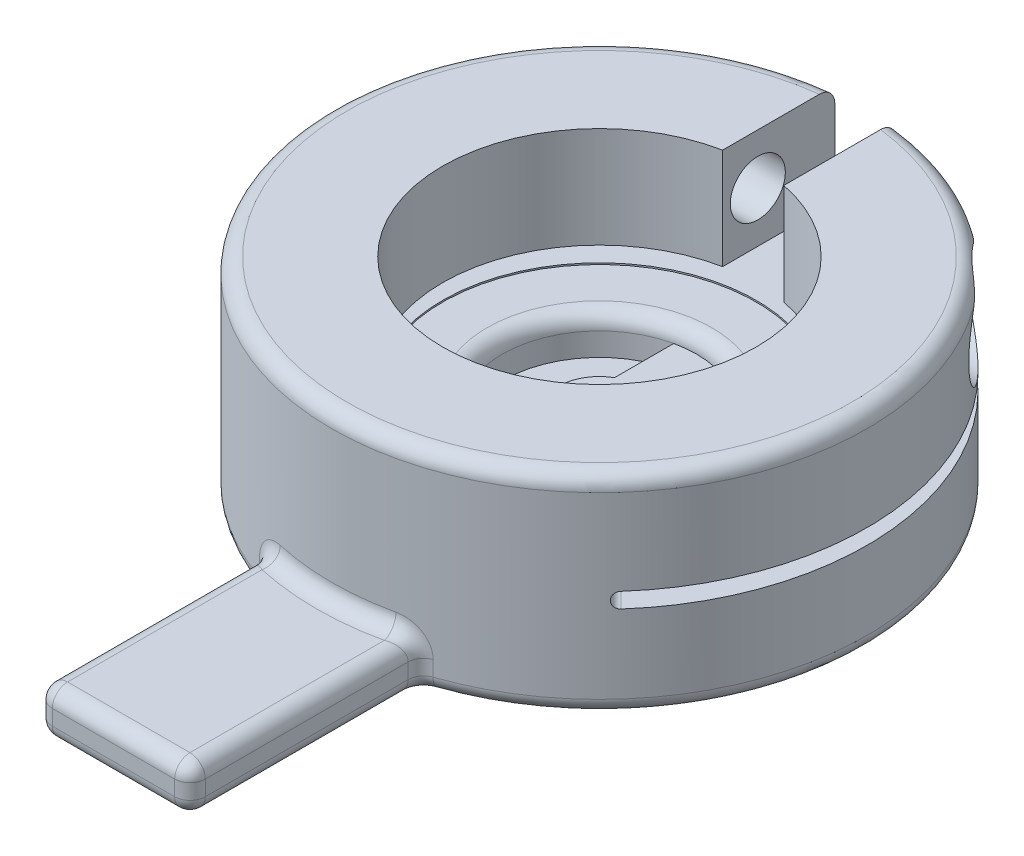
SolidWorks part; units mm, degrees
ref_plane "Front Plane" through (0, 0, 0) normal (0, 0, 1) x (1, 0, 0)
ref_plane "Top Plane" through (0, 0, 0) normal (0, 1, 0) x (1, 0, 0)
ref_plane "Right Plane" through (0, 0, 0) normal (1, 0, 0) x (0, 0, -1)
sketch "Sketch1" plane through (0, 0, 0) normal (0, 1, 0) x (1, 0, 0)
  circle A0 centre (0, 0) radius 17.5
  dimension "D1" = 35
extrude "Boss-Extrude1" add sketch "Sketch1" along normal blind 6.1
sketch "Sketch2" plane through (0, 6.1, 0) normal (0, 1, 0) x (1, 0, 0)
  circle A0 centre (0, 0) radius 10.25
  dimension "D1" = 20.5
extrude "Cut-Extrude1" cut sketch "Sketch2" against normal offset from surface (0.1 mm away) 6 up to face at (0, 0, 17.5)
sketch "Sketch3" plane through (0, 6, 0) normal (0, 1, 0) x (1, 0, 0)
  circle A0 centre (0, 0) radius 6.35
  dimension "D1" = 12.7
extrude "Cut-Extrude2" cut sketch "Sketch3" against normal blind 2.5
sketch "Sketch4" plane through (0, 3.5, 0) normal (0, 1, 0) x (1, 0, 0)
  line L0 (-1.35, 6.2048) -> (-1.35, 2.3383)
  line L2 (1.35, 2.3383) -> (1.35, 6.2048)
  line L3 (-1.35, -2.3383) -> (-1.35, -6.2048)
  line L5 (1.35, -2.3383) -> (1.35, -6.2048)
  arc A0 (-1.35, 6.2048) -> (1.35, 6.2048) centre (0, 0) cw
  circle A1 centre (0, 0) radius 6.35 construction
  arc A2 (1.35, -2.3383) -> (1.35, 2.3383) centre (0, 0) ccw
  circle A7 centre (0, 0) radius 6.35 construction
  arc A8 (-1.35, -6.2048) -> (1.35, -6.2048) centre (0, 0) ccw
  arc A9 (-1.35, 2.3383) -> (-1.35, -2.3383) centre (0, 0) ccw
  dimension "D1" = 2.7
  dimension "D2" = 2.7
extrude "Boss-Extrude2" add sketch "Sketch4" along normal blind 1.5
sketch "Sketch7" plane through (0, 0, 0) normal (0, -1, 0) x (1, 0, 0)
  line L1 (-5, 16.7705) -> (5, 16.7705)
  line L2 (-5, 16.7705) -> (-5, 31.7705)
  line L3 (-5, 31.7705) -> (5, 31.7705)
  line L4 (5, 16.7705) -> (5, 31.7705)
  circle A0 centre (0, 0) radius 17.5 construction
  point P7 (0, 16.7705)
  dimension "D1" = 15
  dimension "D2" = 10
extrude "Boss-Extrude4" add sketch "Sketch7" against normal blind 3
sketch "Sketch10" plane through (0, 6.1, 0) normal (0, 1, 0) x (1, 0, 0)
  line L0 (12.3744, -12.3744) -> (0, 0) construction
  line L1 (0, 0) -> (-12.3744, -12.3744) construction
  line L2 (-12.3744, -12.3744) -> (-7.2478, -7.2478)
  line L3 (7.2478, -7.2478) -> (12.3744, -12.3744)
  arc A2 (7.2478, -7.2478) -> (-7.2478, -7.2478) centre (0, 0) cw
  circle A3 centre (0, 0) radius 10.25 construction
  arc A4 (12.3744, -12.3744) -> (-12.3744, -12.3744) centre (0, 0) cw
  circle A5 centre (0, 0) radius 17.5 construction
  point P1 (0, 0)
  point P2 (-8.4307, -9.2289)
  point P4 (0, -0.8443)
  point P16 (0, -1.3683)
  dimension "D1" = 90
extrude "Boss-Extrude5" add sketch "Sketch10" along normal blind 1
sketch "Sketch11" plane through (0, 7.1, 0) normal (0, 1, 0) x (1, 0, 0)
  line L0 (-2, 17.3853) -> (-2, 10.053)
  line L2 (2, 10.053) -> (2, 17.3853)
  arc A0 (-2, 17.3853) -> (2, 17.3853) centre (0, 0) ccw
  arc A1 (-2, 10.053) -> (2, 10.053) centre (0, 0) ccw
  arc A2 (-7.2478, -7.2478) -> (7.2478, -7.2478) centre (0, 0) ccw construction
  arc A3 (-12.3744, -12.3744) -> (12.3744, -12.3744) centre (0, 0) ccw construction
  arc A4 (12.3744, -12.3744) -> (-12.3744, -12.3744) centre (0, 0) ccw construction
  point P1 (2.1572, 0)
  point P12 (0, 0)
  point P15 (-2.5752, 17.3095)
  dimension "D1" = 4
extrude "Boss-Extrude6" add sketch "Sketch11" along normal blind 6.6
sketch "Sketch12" plane through (0, 0, 0) normal (1, 0, 0) x (0, 0, -1)
  line L0 (10.053, 13.7) -> (10.053, 7.1) construction
  line L2 (12.353, 7.1) -> (12.353, 13.7) construction
  line L3 (17.3853, 13.7) -> (-17.5, 13.7) construction
  line L4 (-12.3744, 7.1) -> (17.3853, 7.1) construction
  circle A0 centre (12.353, 10.4) radius 1.8
  point P2 (0, 0)
  point P3 (13.0554, 11.0887)
  point P4 (0, 0)
  point P5 (0, 0)
  point P6 (13.4869, 12.3)
  point P7 (12.353, 10.4)
  point P11 (0, 0)
  point P15 (12.353, 10.4)
  point P18 (0, 0)
  dimension "D1" = 3.6
  dimension "D2" = 2.3
extrude "Cut-Extrude7" cut sketch "Sketch12" against normal through all both and the other way through all
sketch "Sketch13" plane through (0, 0, 0) normal (1, 0, 0) x (0, 0, -1)
  circle A0 centre (12.353, 10.4) radius 3
  dimension "D1" = 6
extrude "Cut-Extrude8" cut sketch "Sketch13" along normal up to next from offset 8
sketch "Sketch14" plane through (0, 0, 0) normal (1, 0, 0) x (0, 0, -1)
  line L1 (15.5284, 10.4) -> (13.9407, 13.15)
  line L2 (13.9407, 13.15) -> (10.7653, 13.15)
  line L3 (10.7653, 13.15) -> (9.1776, 10.4)
  line L4 (9.1776, 10.4) -> (10.7653, 7.65)
  line L5 (10.7653, 7.65) -> (13.9407, 7.65)
  line L6 (13.9407, 7.65) -> (15.5284, 10.4)
  circle A0 centre (12.353, 10.4) radius 2.75 construction
  point P1 (0, 0)
  point P10 (15.237, 14.3481)
  point P11 (15.8342, 15.3823)
  dimension "D1" = 5.5
extrude "Cut-Extrude9" cut sketch "Sketch14" against normal up to next from offset 8 offset against normal yes
fillet "Fillet1" radius 1 18 edges at (0, 6, 6.35) (0, 3, 17.5) (-5, 3, 24.2705) (0, 3, 31.7705) (5, 3, 24.2705) (5, 1.5, 16.7705) (5, 1.5, 31.7705) (-5, 1.5, 31.7705) (-5, 1.5, 16.7705) (5, 0, 24.2705) (-5, 0, 24.2705) (0, 0, -17.5) (0, 0, 31.7705) (-9.8111, 6.1, 9.8111) (-9.8111, 7.1, 9.8111) (9.8111, 6.1, 9.8111) (9.8111, 7.1, 9.8111) (0, 13.7, 17.5)
fillet "Fillet2" radius 0.5 2 edges at (9.9054, 6.6, 9.7159) (-9.9054, 6.6, 9.7159)
equation "\"D2@Sketch12\"=\"D1@Sketch12\"/2+0.5"
